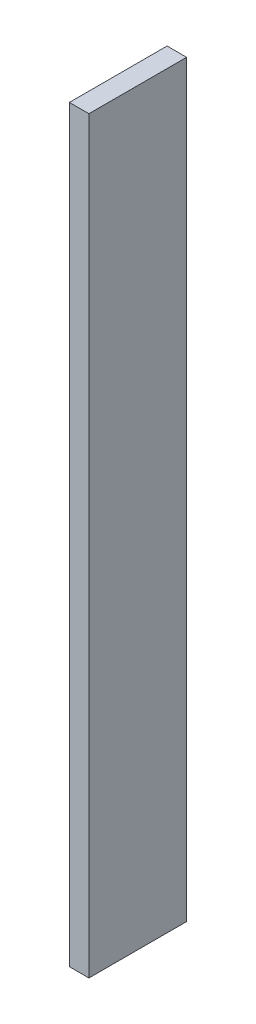
SolidWorks part; units mm, degrees
ref_plane "Plan de face" through (0, 0, 0) normal (0, 0, 1) x (1, 0, 0)
ref_plane "Plan de dessus" through (0, 0, 0) normal (0, 1, 0) x (1, 0, 0)
ref_plane "Plan de droite" through (0, 0, 0) normal (1, 0, 0) x (0, 0, -1)
sketch "Esquisse1" plane through (0, 0, 0) normal (1, 0, 0) x (0, 0, -1)
  line L1 (-25, -191.5) -> (25, -191.5)
  line L2 (-25, -191.5) -> (-25, 191.5)
  line L3 (-25, 191.5) -> (25, 191.5)
  line L4 (25, -191.5) -> (25, 191.5)
  line L5 (-25, -191.5) -> (25, 191.5) construction
  line L6 (-25, 191.5) -> (25, -191.5) construction
  point P0 (0, 0)
  dimension "D1" = 50
  dimension "D2" = 383
extrude "Boss.-Extru.1" add sketch "Esquisse1" along normal blind 10
